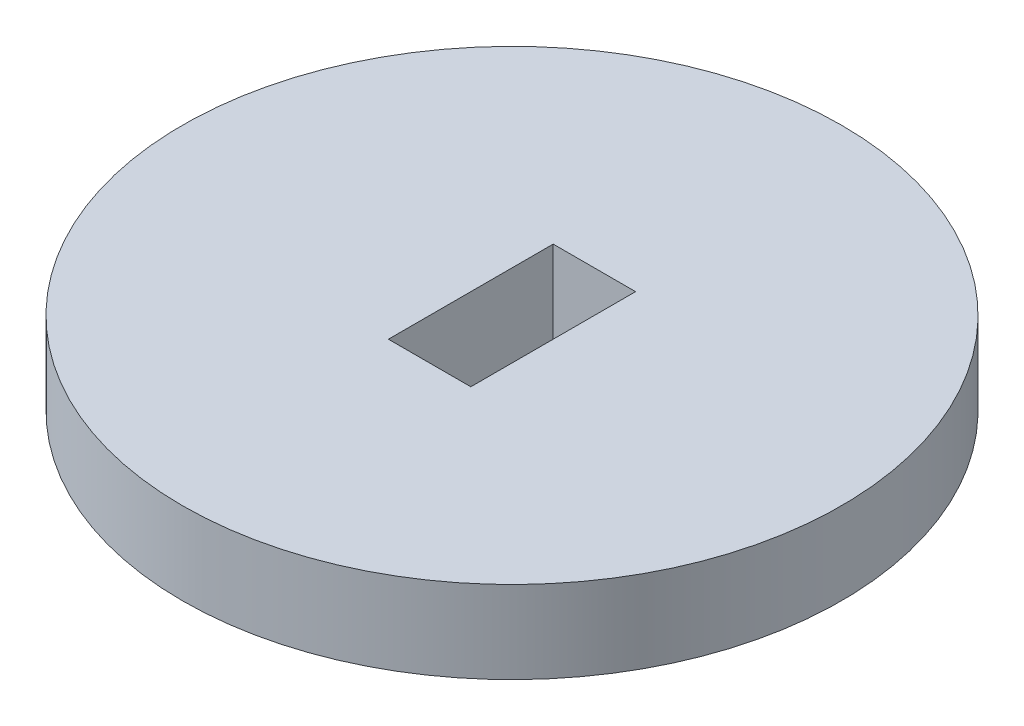
SolidWorks part; units mm, degrees
ref_plane "Front" through (0, 0, 0) normal (0, 0, 1) x (1, 0, 0)
ref_plane "Top" through (0, 0, 0) normal (0, 1, 0) x (1, 0, 0)
ref_plane "Right" through (0, 0, 0) normal (1, 0, 0) x (0, 0, -1)
sketch "Sketch1" plane through (0, 0, 0) normal (0, 1, 0) x (1, 0, 0)
  line L1 (-1.5875, -3.175) -> (1.5875, -3.175)
  line L2 (-1.5875, -3.175) -> (-1.5875, 3.175)
  line L3 (-1.5875, 3.175) -> (1.5875, 3.175)
  line L4 (1.5875, -3.175) -> (1.5875, 3.175)
  line L5 (-1.5875, -3.175) -> (1.5875, 3.175) construction
  line L6 (-1.5875, 3.175) -> (1.5875, -3.175) construction
  circle A0 centre (0, 0) radius 12.7
  dimension "D1" = 25.4
  dimension "D2" = 3.175
  dimension "D3" = 6.35
extrude "Boss-Extrude1" add sketch "Sketch1" along normal blind 3.175
